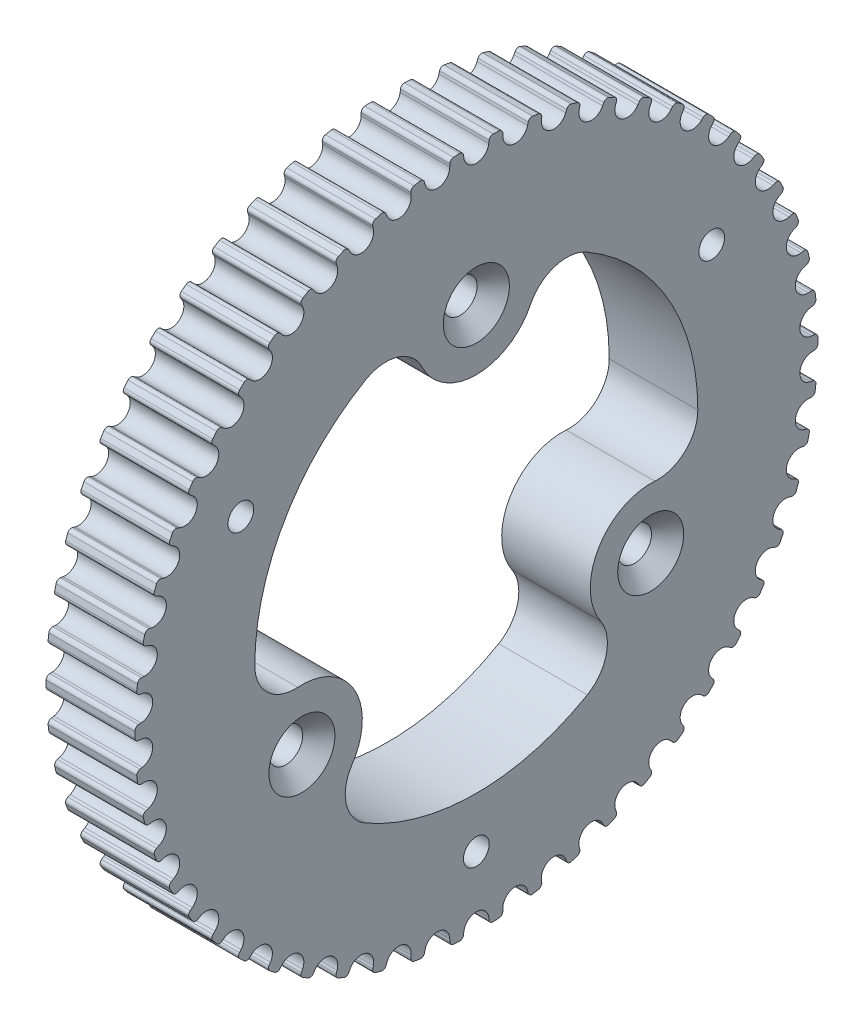
SolidWorks part; units mm, degrees
note: '?' marks a value the reader was unsure of.
ref_plane "前视基准面" through (0, 0, 0) normal (0, 0, 1) x (1, 0, 0)
ref_plane "上视基准面" through (0, 0, 0) normal (0, 1, 0) x (1, 0, 0)
ref_plane "右视基准面" through (0, 0, 0) normal (1, 0, 0) x (0, 0, -1)
sketch "草图1" plane through (0, 0, 0) normal (0, 0, 1) x (1, 0, 0)
  line L0 (0, 0) -> (64.8368, 0) construction
  line L1 (0, 17.5) -> (0, 42.398)
  line L2 (0, 42.398) -> (11, 42.398)
  line L3 (11, 42.398) -> (11, 17.5)
  line L6 (11, 17.5) -> (0, 17.5)
  dimension "B" = 11
  dimension "d" = 35
  dimension "da" = 84.796
revolve "旋转1" add sketch "草图1" angle 360 about L0
sketch "草图6" plane through (0, 0, 0) normal (1, 0, 0) x (0, 0, -1)
  line L0 (0, 0) -> (0, 30.6512) construction
  line L1 (1.5874, 41.9257) -> (1.5484, 41.6079)
  line L2 (2.5667, 42.3202) -> (2.7634, 43.9218)
  line L3 (-2.5667, 42.3202) -> (-2.7634, 43.9218)
  line L4 (-1.5874, 41.9257) -> (-1.5484, 41.6079)
  circle A0 centre (0, 0) radius 42.398 construction
  circle A1 centre (0, 0) radius 40.238 construction
  arc A2 (-1.5484, 41.6079) -> (1.5484, 41.6079) centre (0, 41.798) ccw
  arc A3 (2.7634, 43.9218) -> (-2.7634, 43.9218) centre (0, 0) ccw
  arc A4 (1.5874, 41.9257) -> (2.0874, 42.3466) centre (2.0638, 41.8672) cw
  arc A5 (2.0874, 42.3466) -> (2.5667, 42.3202) centre (0, 0) cw
  arc A6 (-2.0874, 42.3466) -> (-2.5667, 42.3202) centre (0, 0) ccw
  arc A7 (-1.5874, 41.9257) -> (-2.0874, 42.3466) centre (-2.0638, 41.8672) ccw
  point P7 (0, 3.25)
  point P8 (0, 28.4912)
  point P15 (1.6415, 42.3662)
  dimension "D1" = 80.476
  dimension "ra" = 0.48
  dimension "rf" = 1.56
  dimension "hg" = 2.16
  dimension "D3" = 0.48
  dimension "D4" = 1.6136
  dimension "angle" = 14
  dimension "bw" = 3.25
extrude "切除-拉伸2" cut sketch "草图6" along normal up to next
ref_axis "基准轴1" through (-1.4, 0, 0) along (1, 0, 0)?
pattern_circular "阵列(圆周)3" count 54 over 360 about axis through (0, 0, 0) along (1, 0, 0) of "切除-拉伸2"
sketch "草图7" plane through (11, 0, 0) normal (1, 0, 0) x (0, 0, -1)
  circle A0 centre (0, 0) radius 25 construction
  circle A1 centre (0, 25) radius 2.1
  dimension "D1" = 50
  dimension "D2" = 4.2
extrude "切除-拉伸3" cut sketch "草图7" against normal through all
pattern_circular "阵列(圆周)4" count 3 over 360 about axis through (0, 0, 0) along (1, 0, 0) of "切除-拉伸3"
chamfer "倒角1" distance 2 angle 45 3 edges at (11, -14.3187, -20.6006) (11, -10.6813, 22.7006) (11, 25, -2.1)
sketch "草图9" plane through (11, 0, 0) normal (1, 0, 0) x (0, 0, -1)
  circle A0 centre (0, 0) radius 33.75 construction
  circle A1 centre (0, -33.75) radius 1.6
  dimension "D1" = 67.5
  dimension "D2" = 3.2
extrude "切除-拉伸4" cut sketch "草图9" against normal through all
sketch "草图10" plane through (11, 0, 0) normal (1, 0, 0) x (0, 0, -1)
  arc A0 (-19.2754, -19.614) -> (-15.1554, -8.75) centre (-21.6506, -12.5) ccw
  circle A1 centre (0, 0) radius 17.5 construction
  arc A2 (-19.2754, -19.614) -> (19.2754, -19.614) centre (0, 0) ccw
  arc A3 (-15.1554, -8.75) -> (15.1554, -8.75) centre (0, 0) ccw
  arc A5 (15.1554, -8.75) -> (19.2754, -19.614) centre (21.6506, -12.5) ccw
  dimension "D1" = 55
extrude "切除-拉伸5" cut sketch "草图10" against normal through all
pattern_circular "阵列(圆周)5" count 3 over 360 about axis through (0, 0, 0) along (1, 0, 0) of "切除-拉伸5", "切除-拉伸4"
fillet "圆角1" radius 5 6 edges at (5.5, -19.614, -19.2754) (5.5, -19.614, 19.2754) (5.5, -6.886, 26.6239) (5.5, 26.5, 7.3485) (5.5, 26.5, -7.3485) (5.5, -6.886, -26.6239)
equation "\"D1@草图6\" = \"da@草图1\"  - \"hg@草图6\" - \"hg@草图6\""
equation "\"D3@草图6\" = \"ra@草图6\""
